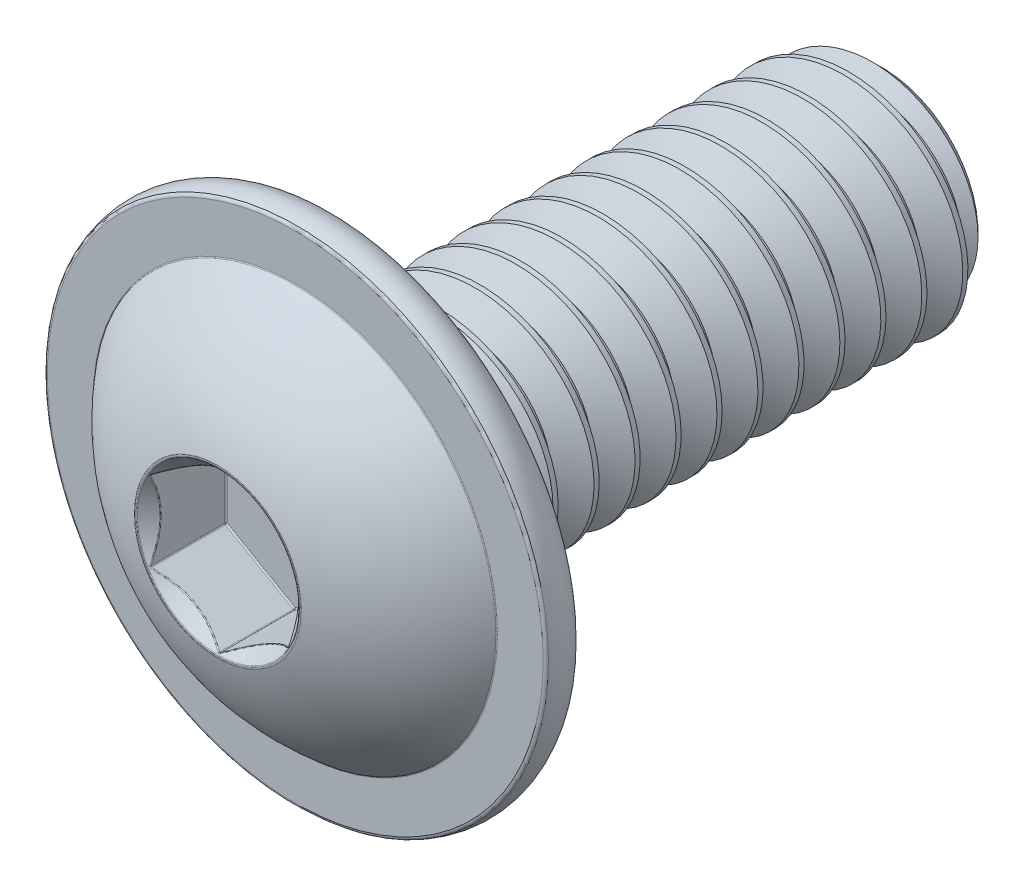
SolidWorks part; units mm, degrees
ref_plane "Front Plane" through (0, 0, 0) normal (0, 0, 1) x (1, 0, 0)
ref_plane "Top Plane" through (0, 0, 0) normal (0, 1, 0) x (1, 0, 0)
ref_plane "Right Plane" through (0, 0, 0) normal (1, 0, 0) x (0, 0, -1)
sketch "Sketch1" plane through (0, 0, 0) normal (1, 0, 0) x (0, 0, -1)
  line L0 (-11.4554, 0) -> (11.4554, 0) construction
  line L1 (11.4554, 0) -> (11.4554, 3.9751)
  line L2 (11.4554, 3.9751) -> (-7.5946, 3.9751)
  line L3 (-7.5946, 3.9751) -> (-7.5946, 0)
  line L4 (11.4554, 0) -> (12.8665, 0) construction
  line L5 (11.4554, 3.2695) -> (10.7498, 3.9751)
  line L6 (-7.5946, 3.9751) -> (-7.5946, 8.7312)
  line L7 (-7.5946, 8.7312) -> (-8.7884, 8.7312)
  line L8 (-8.7884, 8.7312) -> (-8.7884, 7.5374)
  line L9 (-11.4554, 0) -> (-11.4554, 2.7496)
  line L10 (-8.7884, 7.5374) -> (-8.7884, 6.3436) construction
  line L11 (-11.4554, 2.7496) -> (-13.8366, 1.3748)
  line L12 (-13.8366, 1.3748) -> (-13.8367, -1.3748)
  line L13 (-13.8367, -1.3748) -> (-11.4554, -2.7496)
  line L14 (-11.4554, -2.7496) -> (-9.0741, -1.3748)
  line L15 (-9.0741, -1.3748) -> (-9.0742, 1.3748)
  line L16 (-9.0742, 1.3748) -> (-11.4554, 2.7496)
  line L17 (-7.5946, 4.4831) -> (-7.5946, -4.4831) construction
  circle A1 centre (-11.4554, 0) radius 2.3813 construction
  arc A3 (-8.7884, 6.9405) -> (-11.4554, 2.8687) centre (-3.8799, 0.8162) ccw
  point P2 (0, 0)
  point P10 (9.3387, -3.9751)
  point P16 (11.4554, -3.9751)
  point P17 (-7.5946, 8.7312)
  point P18 (11.4554, 3.9751)
  point P20 (9.3387, 3.9751)
  dimension "Head Radii" = 7.8486
  dimension "D1" = 45
  dimension "D3" = 0.7056
  dimension "D4" = 2.1167
  dimension "D2" = 0.1191
sketch "Sketch3" plane through (0, 0, 0) normal (1, 0, 0) x (0, 0, -1)
  line L0 (-7.5946, 3.9751) -> (-7.5946, 8.7312) construction
  line L1 (-7.5946, 8.7312) -> (-8.7884, 8.7312) construction
  line L2 (-7.5946, 8.7312) -> (-7.5946, 4.4831) construction
  line L3 (-11.4554, 0) -> (-11.4554, 2.7496) construction
  line L4 (-7.5946, 3.9751) -> (-7.5946, 8.7312) construction
  line L5 (-7.5946, 8.7312) -> (-8.7884, 8.7312) construction
  line L7 (-11.4554, 0) -> (-11.4554, 2.8687)
  line L8 (-7.5946, 3.9751) -> (10.7498, 3.9751) construction
  line L9 (10.7498, 3.9751) -> (11.4554, 3.2695)
  line L10 (11.4554, 3.2695) -> (11.4554, 0)
  line L11 (11.4554, 0) -> (-11.4554, 0)
  line L12 (-8.7884, 6.9405) -> (-8.7884, 8.7312) construction
  line L13 (-7.0866, 3.9751) -> (10.7498, 3.9751)
  line L14 (-8.7884, 6.9405) -> (-8.7884, 8.6119)
  line L15 (-7.5946, 4.4831) -> (-7.5946, 8.4925)
  line L16 (-8.7884, 8.7312) -> (-8.7884, 8.4925) construction
  arc A0 (-8.7884, 6.9405) -> (-11.4554, 2.8687) centre (-3.8799, 0.8162) ccw construction
  arc A2 (-8.7884, 8.6119) -> (-7.5946, 8.4925) centre (-8.2855, 7.6123) cw
  arc A4 (-8.7884, 6.9405) -> (-11.4554, 2.8687) centre (-3.8799, 0.8162) ccw
  arc A5 (-7.5946, 4.4831) -> (-7.0866, 3.9751) centre (-7.0866, 4.4831) ccw
  dimension "D1" = 0.2388
revolve "Revolve1" add sketch "Sketch3" angle 360 about L11
sketch "Sketch4" plane through (0, 0, 11.4554) normal (0, 0, 1) x (1, 0, 0)
  line L13 (0, 2.7496) -> (-2.3813, 1.3748)
  line L14 (-2.3813, 1.3748) -> (-2.3813, -1.3748)
  line L15 (-2.3813, -1.3748) -> (0, -2.7496)
  line L16 (0, -2.7496) -> (2.3812, -1.3748)
  line L17 (2.3812, -1.3748) -> (2.3812, 1.3748)
  line L18 (2.3812, 1.3748) -> (0, 2.7496)
  circle A0 centre (0, 0) radius 2.3813 construction
  dimension "D1" = 4.7625
extrude "Cut-Extrude1" cut sketch "Sketch4" against normal up to surface (2.667 mm away) up to face at (-6.9405, 0, 8.7884)
sketch "Sketch5" plane through (0, 0, 11.4554) normal (0, 0, 1) x (1, 0, 0)
  line L0 (0, 2.7496) -> (0, 2.7973) construction
  circle A1 centre (0, 0) radius 2.7973
  dimension "D1" = 0.0476
extrude "Cut-Extrude2" cut sketch "Sketch5" against normal up to surface (2.667 mm away) draft 45 up to face at (0, 0, 8.7884)
fillet "Fillet3" radius 0.0476 21 edges at (-1.3402, -1.9759, 11.0456) (1.0411, -2.1486, 11.0456) (0, -2.7496, 10.0981) (2.3812, -0.029, 11.0396) (2.3812, -1.3748, 10.0981) (1.3402, 1.9759, 11.0456) (2.3812, 1.3748, 10.0981) (2.3812, 0, 8.7884) (1.1906, -2.0622, 8.7884) (-1.1906, -2.0622, 8.7884) (1.1906, 2.0622, 8.7884) (-2.3813, 0, 8.7884) (-2.3813, -1.3748, 10.0981) (-2.3813, -0.029, 11.0396) (-1.1906, 2.0622, 8.7884) (-2.3813, 1.3748, 10.0981) (-1.0411, 2.1486, 11.0456) (0, 2.7496, 10.0981) (-2.8687, 0, 11.4554) (2.7973, 0, 11.4554) (-6.9405, 0, 8.7884)
fillet "Fillet4" radius 0.1194 2 edges at (-8.4925, 0, 7.5946) (-8.6119, 0, 8.7884)
sketch "Reference Sketch1" plane through (0, 0, 0) normal (0, 0, 1) x (1, 0, 0)
  circle A0 centre (0, 0) radius 8.7312 construction
ref_plane "Plane1" through (0, 0, 7.0866) normal (0, 0, 1) x (1, 0, 0)
split "Split1" trim tools "Plane1" bodies to split 106 resulting bodies 108 111
sketch "Sketch6" plane through (0, 0, -11.4554) normal (0, 0, -1) x (-1, 0, 0)
  circle A1 centre (0, 0) radius 3.9751
curve "Helix/Spiral1" pitch 1.4111 height 21.1667 turns 15
sketch "Sketch7" plane through (0, 0, 0) normal (1, 0, 0) x (0, 0, -1)
  line L0 (11.3672, 4.1279) -> (12.0728, 2.9058) construction
  line L1 (12.0728, 2.9058) -> (12.7783, 4.1279) construction
  line L2 (12.7783, 4.1279) -> (11.3672, 4.1279) construction
  line L3 (11.4113, 4.0515) -> (12.7342, 4.0515)
  line L4 (12.7342, 4.0515) -> (12.161, 3.0586)
  line L5 (12.161, 3.0586) -> (11.9846, 3.0586)
  line L6 (11.9846, 3.0586) -> (11.4113, 4.0515)
  line L7 (12.0728, 3.0586) -> (12.0728, 2.9058) construction
  line L8 (11.4554, 3.9751) -> (12.6901, 3.9751) construction
  line L9 (12.0728, 4.1279) -> (12.0728, 3.9751) construction
  point P12 (12.0728, 4.0515)
  dimension "D1" = 1.4111
  dimension "D2" = 0.1764
sweep "Cut-Sweep1" cut profiles "Sketch7" path "Helix/Spiral1" align with end faces yes
sketch "Sketch8" plane through (0, 0, 7.0866) normal (0, 0, 1) x (1, 0, 0)
  circle A2 centre (0, 0) radius 3.9751
  circle A3 centre (0, 0) radius 3.9751
  dimension "D1" = 0
extrude "Boss-Extrude1" add sketch "Sketch8" against normal through all draft 45
equation "\"D3@Sketch1\"=0.5*\"Pitch@Sketch1\""
equation "\"D4@Helix/Spiral1\"=\"Pitch@Sketch1\""
equation "\"D3@Helix/Spiral1\"=\"Pitch@Sketch1\"*1.5+\"Length@Sketch1\""
equation "\"D1@Sketch7\"=\"Pitch@Sketch1\""
equation "\"D2@Sketch7\"=\"D1@Sketch7\"/8"
equation "\"D4@Sketch1\"=\"Pitch@Sketch1\"*1.5"
equation "\"D1@Sketch4\"=\"Drive Size@Sketch1\""
equation "\"D1@Sketch5\"=\"Drive Size@Sketch1\"*0.01"
equation "\"D2@Sketch1\"=\"Drive Size@Sketch1\"*0.025"
equation "\"D1@Fillet3\"=\"Drive Size@Sketch1\"*0.01"
equation "\"D1@Fillet4\"=(\"Head Height@Sketch1\"-\"Hex Key Engagement@Sketch1\")*0.1"
equation "\"D1@Sketch3\"=(\"Head Height@Sketch1\"-\"Hex Key Engagement@Sketch1\")*0.2"
